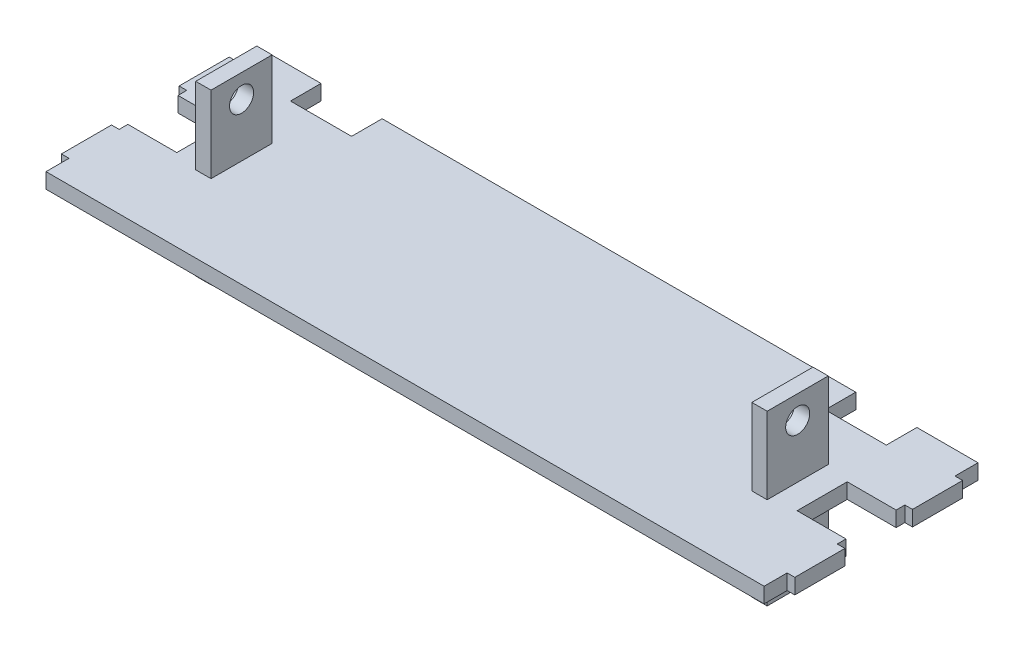
SolidWorks part; units mm, degrees
ref_plane "Front Plane" through (0, 0, 0) normal (0, 0, 1) x (1, 0, 0)
ref_plane "Top Plane" through (0, 0, 0) normal (0, 1, 0) x (1, 0, 0)
ref_plane "Right Plane" through (0, 0, 0) normal (1, 0, 0) x (0, 0, -1)
sketch "Sketch1" plane through (0, 0, 0) normal (0, 1, 0) x (1, 0, 0)
  line L0 (0, 72.39) -> (0, -44.45) construction
  line L1 (149.225, -44.45) -> (-149.225, -44.45)
  line L2 (149.225, -44.45) -> (149.225, -34.8747)
  line L3 (149.225, 44.45) -> (123.825, 44.45)
  line L4 (-149.225, -44.45) -> (-149.225, -34.8747)
  line L5 (149.225, -44.45) -> (-149.225, 44.45) construction
  line L6 (149.225, 44.45) -> (-149.225, -44.45) construction
  line L7 (149.225, 10.414) -> (128.905, 10.414)
  line L9 (149.225, -10.414) -> (128.905, -10.414)
  line L10 (128.905, 10.414) -> (128.905, -10.414)
  line L11 (-123.825, 44.45) -> (-149.225, 44.45)
  line L13 (-149.225, -10.414) -> (-128.905, -10.414)
  line L14 (-128.905, 10.414) -> (-128.905, -10.414)
  line L15 (-149.225, 10.414) -> (-128.905, 10.414)
  line L17 (-127, 0) -> (127, 0) construction
  line L18 (-149.225, 14.0467) -> (-152.4, 14.0467)
  line L20 (-149.225, 34.8747) -> (-152.4, 34.8747)
  line L21 (-152.4, 14.0467) -> (-152.4, 34.8747)
  line L22 (-149.225, -34.8747) -> (-152.4, -34.8747)
  line L23 (-152.4, -14.0467) -> (-152.4, -34.8747)
  line L24 (-149.225, -14.0467) -> (-152.4, -14.0467)
  line L27 (149.225, -14.0467) -> (152.4, -14.0467)
  line L28 (152.4, -14.0467) -> (152.4, -34.8747)
  line L29 (149.225, -34.8747) -> (152.4, -34.8747)
  line L30 (149.225, 34.8747) -> (152.4, 34.8747)
  line L31 (152.4, 14.0467) -> (152.4, 34.8747)
  line L32 (149.225, 14.0467) -> (152.4, 14.0467)
  line L34 (-149.225, 34.8747) -> (-149.225, 44.45)
  line L35 (-149.225, -14.0467) -> (-149.225, -10.414)
  line L36 (149.225, 34.8747) -> (149.225, 44.45)
  line L37 (149.225, -14.0467) -> (149.225, -10.414)
  line L38 (-149.225, 10.414) -> (-149.225, 14.0467)
  line L39 (149.225, 10.414) -> (149.225, 14.0467)
  line L40 (-123.825, 44.45) -> (-123.825, 31.75)
  line L41 (-123.825, 31.75) -> (-98.425, 31.75)
  line L42 (-98.425, 44.45) -> (-98.425, 31.75)
  line L44 (98.425, 44.45) -> (98.425, 31.75)
  line L45 (98.425, 31.75) -> (123.825, 31.75)
  line L46 (123.825, 44.45) -> (123.825, 31.75)
  line L47 (98.425, 44.45) -> (-98.425, 44.45)
  point P0 (0, 0)
  point P6 (127, 0)
  dimension "D1" = 298.45
  dimension "D2" = 88.9
  dimension "D3" = 20.828
  dimension "D5" = 3.175
  dimension "D6" = 20.828
  dimension "D4" = 20.32
  dimension "D7" = 12.7
  dimension "D8" = 25.4
  dimension "D9" = 25.4
  dimension "D10" = 12.7
  dimension "D12" = 25.4
  dimension "D11" = 25.4
  dimension "D13" = 304.8
  dimension "D14" = 14.0467
  dimension "D15" = 10.414
extrude "Boss-Extrude1" add sketch "Sketch1" along normal mid plane 6.35
sketch "Sketch2" plane through (0, 0, 0) normal (0, 1, 0) x (1, 0, 0)
  line L1 (112.395, -12.7) -> (118.745, -12.7)
  line L2 (112.395, -12.7) -> (112.395, 12.7)
  line L3 (112.395, 12.7) -> (118.745, 12.7)
  line L4 (118.745, -12.7) -> (118.745, 12.7)
  line L5 (112.395, -12.7) -> (118.745, 12.7) construction
  line L6 (112.395, 12.7) -> (118.745, -12.7) construction
  line L7 (0, 44.45) -> (0, -44.45) construction
  line L8 (98.425, 44.45) -> (-98.425, 44.45) construction
  line L13 (128.905, -10.414) -> (128.905, 10.414) construction
  line L14 (-149.225, -44.45) -> (149.225, -44.45) construction
  line L15 (-112.395, -12.7) -> (-112.395, 12.7)
  line L16 (-112.395, -12.7) -> (-118.745, -12.7)
  line L17 (-118.745, -12.7) -> (-118.745, 12.7)
  line L18 (-112.395, 12.7) -> (-118.745, 12.7)
  point P0 (115.57, 0)
  point P10 (128.905, 0)
  dimension "D2" = 10.16
  dimension "D4" = 25.4
  dimension "D5" = 6.35
extrude "Boss-Extrude2" add sketch "Sketch2" along normal mid plane 70.104
sketch "Sketch5" plane through (-118.745, 0, 0) normal (-1, 0, 0) x (0, 0, 1)
  line L0 (0, 25.4) -> (0, -25.4) construction
  line L1 (-44.45, 0) -> (44.45, 0) construction
  line L2 (-44.45, 3.175) -> (-44.45, -3.175) construction
  line L3 (44.45, 3.175) -> (44.45, -3.175) construction
  circle A0 centre (0, 25.4) radius 5.0038
  circle A1 centre (0, -25.4) radius 5.0038
  dimension "D2" = 10.0076
  dimension "D1" = 25.4
extrude "Cut-Extrude1" cut sketch "Sketch5" against normal through all both and the other way through all
equation "\"length\"= \"Avionics_Board_Length\""
equation "\"width\"=3.5"
equation "\"height\"= 0.25"
equation "\"D2@Sketch1\"=\"width\""
equation "\"eyebolt width\"= 0.82"
equation "\"eyebolt length\"= 0.8"
equation "\"D3@Sketch1\"=\"eyebolt width\""
equation "\"D4@Sketch1\"=\"eyebolt length\""
equation "\"lead screw holder height\"= 2.76"
equation "\"lead screw diameter\"=0.394"
equation "\"distance from holders to board\"=0.4"
equation "\"D2@Sketch5\"=\"lead screw diameter\""
equation "\"Mid_Coupler_Length\"= 12in"
equation "\"Avionics_Bulkhead_Thickness\"= 0.25in"
equation "\"Avionics_Bulkhead_Lip\"= 0.125in"
equation "\"Avionics_Board_Length\"= \"Mid_Coupler_Length\" - 2*\"Avionics_Bulkhead_Lip\""
equation "\"Body_Tube_OD\"= 4.024in"
equation "\"D1@Sketch1\"=\"length\""
equation "\"Lead_Screw_Dist\"= 2in"
equation "\"D1@Sketch5\"=\"Lead_Screw_Dist\"/2"
